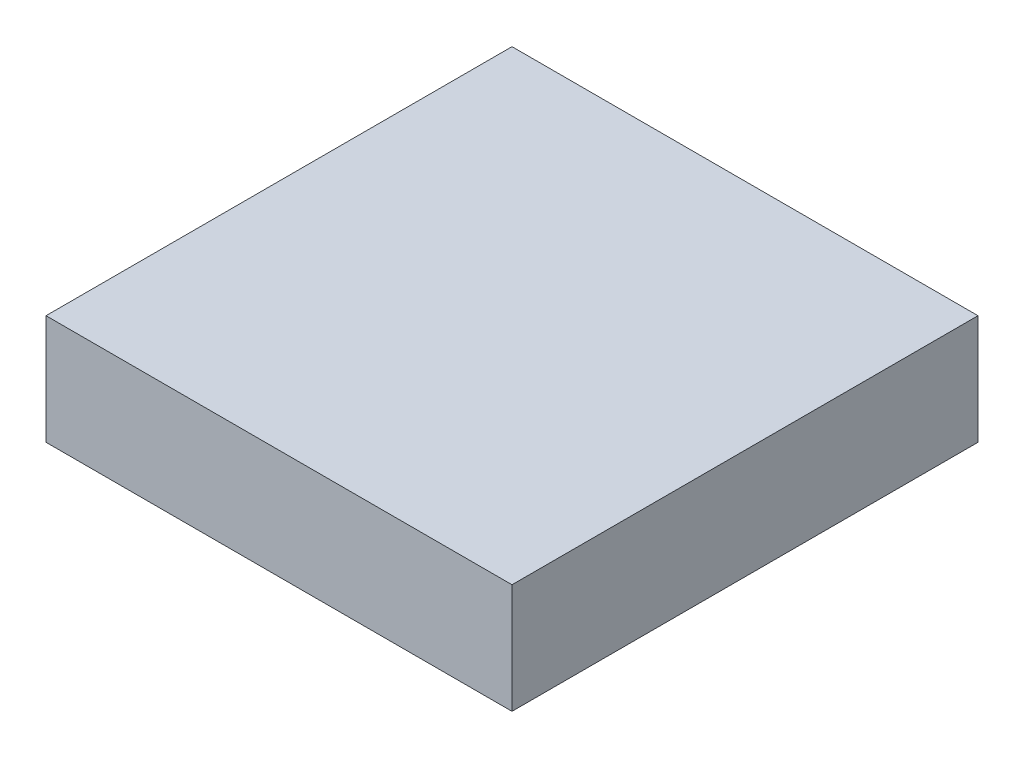
SolidWorks part; units mm, degrees
material "Balsa"
ref_plane "Front Plane" through (0, 0, 0) normal (0, 0, 1) x (1, 0, 0)
ref_plane "Top Plane" through (0, 0, 0) normal (0, 1, 0) x (1, 0, 0)
ref_plane "Right Plane" through (0, 0, 0) normal (1, 0, 0) x (0, 0, -1)
sketch "Sketch1" plane through (0, 0, 0) normal (0, 1, 0) x (1, 0, 0)
  line L1 (0, 0) -> (340, 0)
  line L2 (0, 0) -> (0, -340)
  line L3 (0, -340) -> (340, -340)
  line L4 (340, 0) -> (340, -340)
  dimension "D1" = 340
  dimension "D2" = 340
extrude "Boss-Extrude1" add sketch "Sketch1" along normal blind 80
